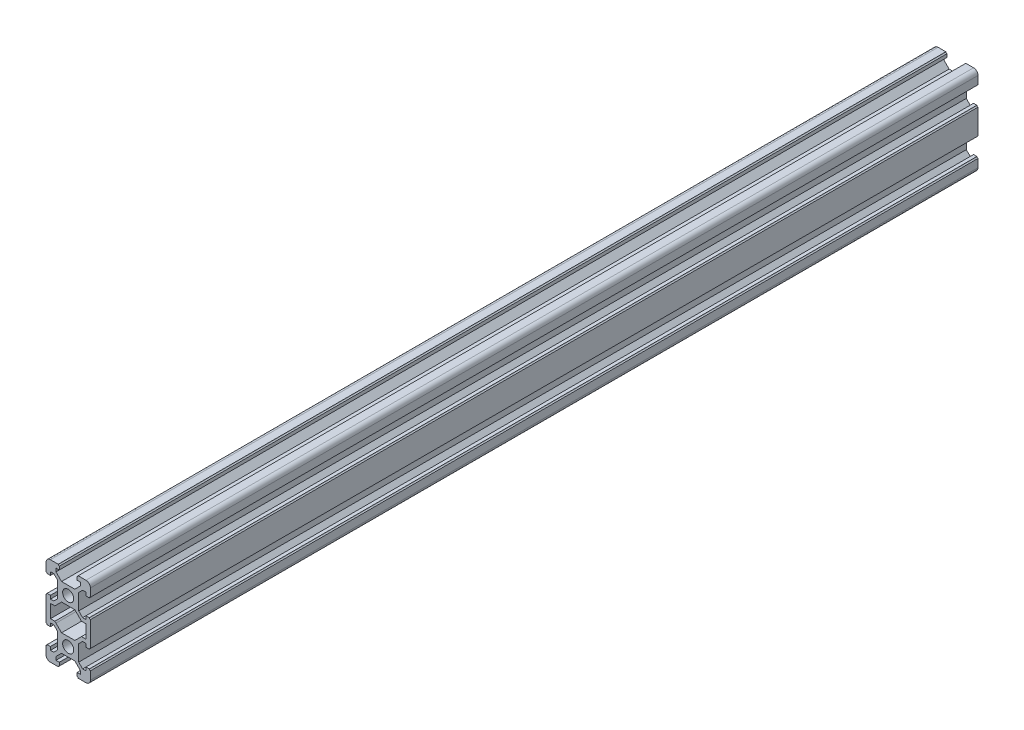
SolidWorks part; units mm, degrees
ref_plane "Спереди" through (0, 0, 0) normal (0, 0, 1) x (1, 0, 0)
ref_plane "Сверху" through (0, 0, 0) normal (0, 1, 0) x (1, 0, 0)
ref_plane "Справа" through (0, 0, 0) normal (1, 0, 0) x (0, 0, -1)
sketch "Эскиз1" plane through (0, 0, 0) normal (0, 0, 1) x (1, 0, 0)
  line L0 (0, 0) -> (10, 0) construction
  line L1 (10, 0) -> (10, 20) construction
  line L2 (10, 20) -> (0, 20) construction
  line L3 (0, 20) -> (0, 0) construction
  line L4 (0, 14) -> (3, 14)
  line L5 (3, 14) -> (5.5, 16.5)
  line L6 (5.5, 16.5) -> (5.5, 18)
  line L7 (5.5, 18) -> (4, 18)
  line L8 (4, 18) -> (4, 20)
  line L9 (4, 20) -> (10, 20)
  line L10 (10, 20) -> (10, 13.8581)
  line L11 (10, 13.8581) -> (8, 13.8581)
  line L12 (8, 13.8581) -> (8, 15.3581)
  line L13 (8, 15.3581) -> (6.5, 15.3581)
  line L14 (6.5, 15.3581) -> (4.7405, 13.5985)
  line L15 (5.5, 17.25) -> (0, 17.25) construction
  line L16 (4, 19) -> (0, 19) construction
  line L17 (8, 14.6081) -> (0, 14.6081) construction
  line L18 (0, 10) -> (10, 10) construction
  line L19 (1.5, 14) -> (1.5, 10) construction
  line L20 (4.7405, 13.5985) -> (4.7405, 6.4015)
  line L21 (3, 6) -> (5.5, 3.5)
  line L22 (0, 6) -> (3, 6)
  line L23 (8, 4.6419) -> (6.5, 4.6419)
  line L24 (6.5, 4.6419) -> (4.7405, 6.4015)
  line L25 (10, 0) -> (10, 6.1419)
  line L26 (10, 6.1419) -> (8, 6.1419)
  line L27 (8, 6.1419) -> (8, 4.6419)
  line L28 (5.5, 3.5) -> (5.992, 3)
  line L29 (8, 0) -> (8, 3)
  line L30 (8, 0) -> (10, 0)
  line L31 (0, 6) -> (0, 7.5)
  line L32 (0, 12.5) -> (0, 14)
  line L33 (8, 3) -> (5.992, 3)
  line L34 (5.992, 3) -> (5.992, 0) construction
  circle A0 centre (0, 10) radius 2.5
  circle A4 centre (10, 6.1419) radius 0.5
  circle A5 centre (10, 13.8581) radius 0.5
  circle A6 centre (4, 20) radius 0.5
  point P34 (4.7405, 10)
  dimension "D3" = 5
  dimension "D11" = 1
  dimension "D12" = 1
  dimension "D13" = 1
  dimension "D1" = 20
  dimension "D2" = 10
  dimension "D4" = 5.5
  dimension "D5" = 4
  dimension "D6" = 8
  dimension "D7" = 1.5
  dimension "D8" = 4
  dimension "D9" = 135
  dimension "D10" = 3
extrude "Бобышка-Вытянуть1" add sketch "Эскиз1" along normal blind 200 and the other way blind 200 contours A0 L31 L22 L21 L28 L30 L25 L26 L27 L23 L24 L20 L14 L13 L12 L11 L10 L9 L8 L7 L6 L5 L4 L32 region at (1.5, 13.7764, 0)
mirror "Зеркальное отражение1" about plane through (0, 0, 0) normal (1, 0, 0) of "Бобышка-Вытянуть1"
mirror "Зеркальное отражение2" about plane through (0, 0, 0) normal (0, 1, 0) of "Зеркальное отражение1"
fillet "Скругление1" radius 2 4 edges at (-10, -20, 0) (10, -20, 0) (10, 20, 0) (-10, 20, 0)
